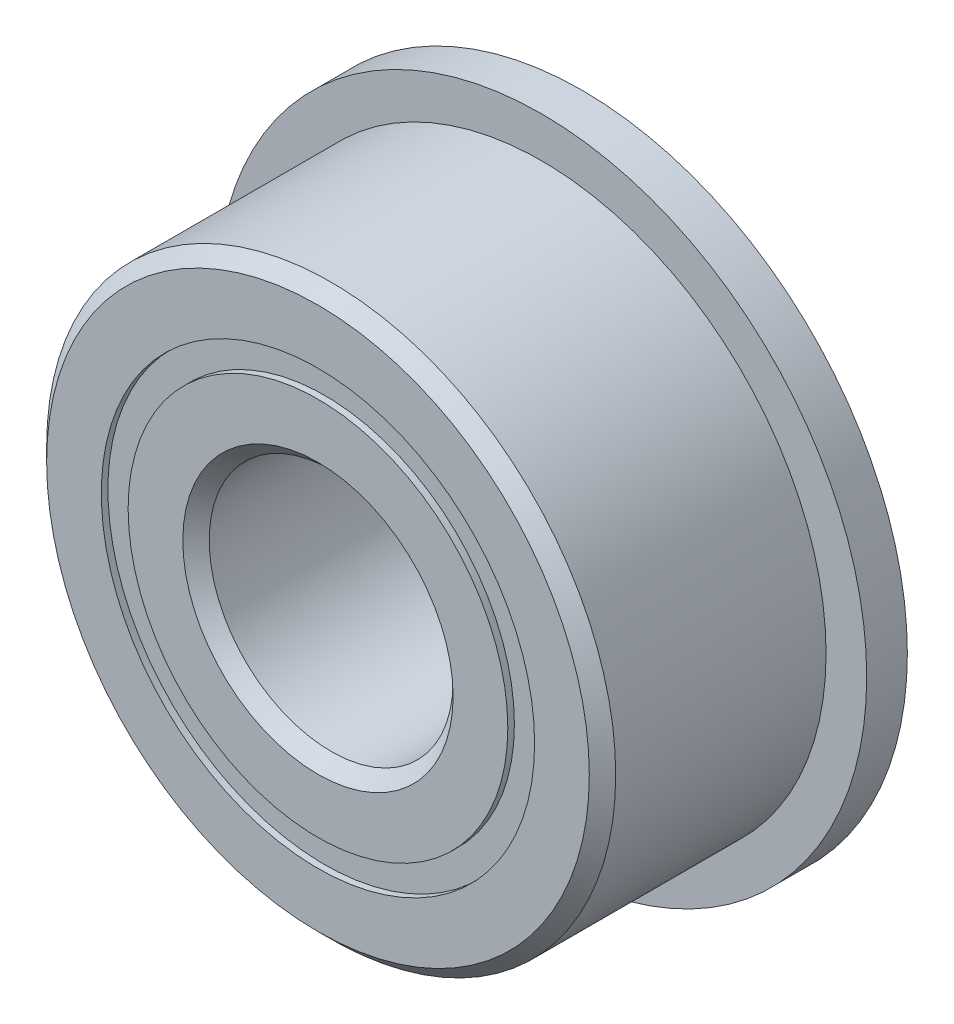
SolidWorks part; units mm, degrees
ref_plane "Front Plane" through (0, 0, 0) normal (0, 0, 1) x (1, 0, 0)
ref_plane "Top Plane" through (0, 0, 0) normal (0, 1, 0) x (1, 0, 0)
ref_plane "Right Plane" through (0, 0, 0) normal (1, 0, 0) x (0, 0, -1)
sketch "Sketch1" plane through (0, 0, 0) normal (1, 0, 0) x (0, 0, -1)
  line L0 (-5.1594, 0) -> (5.1594, 0) construction
  line L1 (0, 11.1125) -> (0, -11.1125) construction
  line L2 (4.6434, 11.1125) -> (-4.6434, 11.1125)
  line L3 (-4.6434, 11.1125) -> (-5.1594, 10.5966)
  line L4 (-5.1594, 10.5966) -> (-5.1594, 8.4609)
  line L5 (-5.1594, 8.4609) -> (-2.2931, 8.4609)
  line L6 (5.1594, 8.4609) -> (2.2931, 8.4609)
  line L7 (5.1594, 10.5966) -> (5.1594, 8.4609)
  line L8 (4.6434, 11.1125) -> (5.1594, 10.5966)
  line L9 (0, 11.1125) -> (0, 7.9375) construction
  line L10 (0, 7.9375) -> (0, 4.7625) construction
  arc A0 (-2.2931, 8.4609) -> (2.2931, 8.4609) centre (0, 7.9375) cw
  point P14 (0, 4.7625)
  dimension "D3" = 4.5861
  dimension "D1" = 45
  dimension "Width" = 10.3187
  dimension "OD" = 22.225
  dimension "D2" = 0.5159
  dimension "Shaft Dia" = 9.525
  dimension "D4" = 0.5234
revolve "Revolve1" add sketch "Sketch1" angle 360 about L0
sketch "Sketch3" plane through (0, 0, 0) normal (1, 0, 0) x (0, 0, -1)
  line L0 (-5.1594, 7.4141) -> (-2.2931, 7.4141)
  line L1 (0, 11.1125) -> (0, -11.1125) construction
  line L2 (-5.1594, 10.5966) -> (-5.1594, 8.4609) construction
  line L3 (-5.1594, 7.4141) -> (-5.1594, 5.2784)
  line L4 (-4.6434, 11.1125) -> (-5.1594, 10.5966) construction
  line L5 (-5.1594, 5.2784) -> (-4.6434, 4.7625)
  line L6 (-4.6434, 4.7625) -> (4.6434, 4.7625)
  line L7 (4.6434, 11.1125) -> (4.6434, -11.1125) construction
  line L8 (4.6434, 4.7625) -> (5.1594, 5.2784)
  line L9 (5.1594, -10.5966) -> (5.1594, 10.5966) construction
  line L10 (5.1594, 5.2784) -> (5.1594, 7.4141)
  line L11 (5.1594, 7.4141) -> (2.2931, 7.4141)
  line L13 (4.6434, 11.1125) -> (5.1594, 10.5966) construction
  arc A0 (2.2931, 8.4609) -> (-2.2931, 8.4609) centre (0, 7.9375) ccw construction
  arc A1 (2.2931, 7.4141) -> (-2.2931, 7.4141) centre (0, 7.9375) cw
revolve "Revolve3" add sketch "Sketch3" angle 360 about L0
sketch "Sketch4" plane through (0, 0, 0) normal (1, 0, 0) x (0, 0, -1)
  line L0 (-2.352, 7.9375) -> (2.352, 7.9375)
  arc A2 (-2.352, 7.9375) -> (2.352, 7.9375) centre (0, 7.9375) cw
  arc A3 (2.2931, 8.4609) -> (-2.2931, 8.4609) centre (0, 7.9375) ccw construction
revolve "Revolve4" add sketch "Sketch4" angle 360 about L0
ref_axis "Axis1" through (0, 0, -5.1594) along (0, 0, 1)
pattern_circular "CirPattern1" count 12 every 30 about axis through (0, 0, -5.1594) along (0, 0, 1) of bodies 104
sketch "Sketch5" plane through (0, 0, 0) normal (1, 0, 0) x (0, 0, -1)
  line L0 (-5.1594, 8.4609) -> (-2.2931, 8.4609) construction
  line L1 (-4.9014, 8.4609) -> (-2.352, 8.4609)
  line L2 (-4.9014, 8.4609) -> (-4.9014, 7.4141)
  line L3 (-4.9014, 7.4141) -> (-2.352, 7.4141)
  line L4 (-2.352, 8.4609) -> (-2.352, 7.4141)
  line L5 (-5.1594, 7.4141) -> (-2.2931, 7.4141) construction
  line L6 (5.1594, 8.4609) -> (2.2931, 8.4609) construction
  line L7 (4.9014, 8.4609) -> (2.352, 8.4609)
  line L8 (4.9014, 8.4609) -> (4.9014, 7.4141)
  line L9 (4.9014, 7.4141) -> (2.352, 7.4141)
  line L10 (2.352, 8.4609) -> (2.352, 7.4141)
  line L11 (5.1594, 7.4141) -> (2.2931, 7.4141) construction
  line L12 (-4.6434, 11.1125) -> (-5.1594, 10.5966) construction
  point P18 (-4.9014, 10.8545)
revolve "Revolve5" add sketch "Sketch5" angle 360 about L0
sketch "Sketch6" plane through (0, 0, 0) normal (1, 0, 0) x (0, 0, -1)
  line L0 (5.1594, 0) -> (-5.1594, 0) construction
  line L1 (5.1594, 8.4609) -> (3.5719, 8.4609)
  line L2 (5.1594, 8.4609) -> (5.1594, 12.7)
  line L3 (5.1594, 12.7) -> (3.5719, 12.7)
  line L4 (3.5719, 8.4609) -> (3.5719, 12.7)
  dimension "Th" = 1.5875
  dimension "Flange OD" = 25.4
revolve "Revolve6" add sketch "Sketch6" angle 360 about L0
equation "\"D2@Sketch1\" = \"Width@Sketch1\"*.05"
equation "\"D3@Sketch1\" = \"Width@Sketch1\"/2.25"
equation "\"D4@Sketch1\" = (((\"OD@Sketch1\"-\"Width@Sketch1\")/2)/3.25)/3.5"
equation "\"D2@CirPattern1\" = 360/\"Balls@CirPattern1\""
